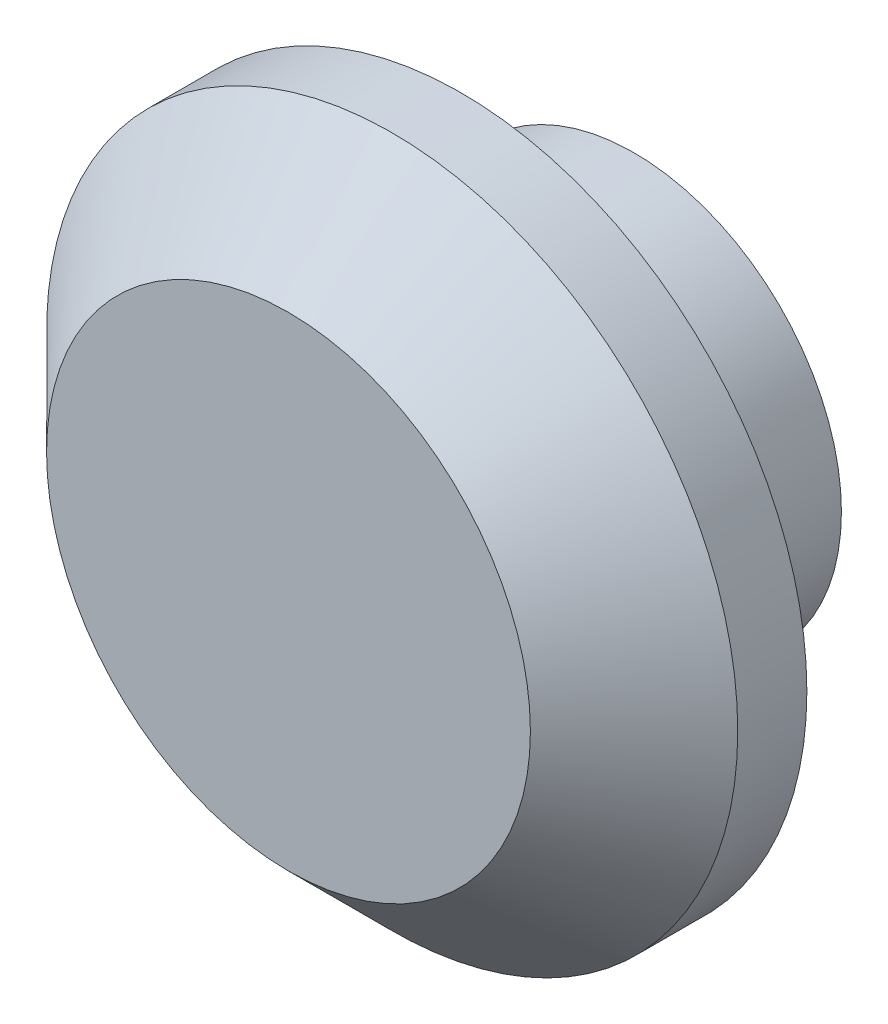
SolidWorks part; units mm, degrees
ref_plane "Front Plane" through (0, 0, 0) normal (0, 0, 1) x (1, 0, 0)
ref_plane "Top Plane" through (0, 0, 0) normal (0, 1, 0) x (1, 0, 0)
ref_plane "Right Plane" through (0, 0, 0) normal (1, 0, 0) x (0, 0, -1)
sketch "Sketch1" plane through (0, 0, 0) normal (0, 0, 1) x (1, 0, 0)
  circle A0 centre (0, 0) radius 3.25 construction
  circle A1 centre (0, 0) radius 3.25
  circle A2 centre (0, 0) radius 6 construction
  circle A3 centre (0, 0) radius 6
extrude "Boss-Extrude1" add sketch "Sketch1" against normal blind 5 and the other way blind 5
sketch "Sketch2" plane through (0, 0, 0) normal (0, 0, 1) x (1, 0, 0)
  circle A0 centre (0, 0) radius 10
extrude "Boss-Extrude2" add sketch "Sketch2" along normal blind 5
chamfer "Chamfer1" distance 3 angle 45 1 edges at (10, 0, 5)
